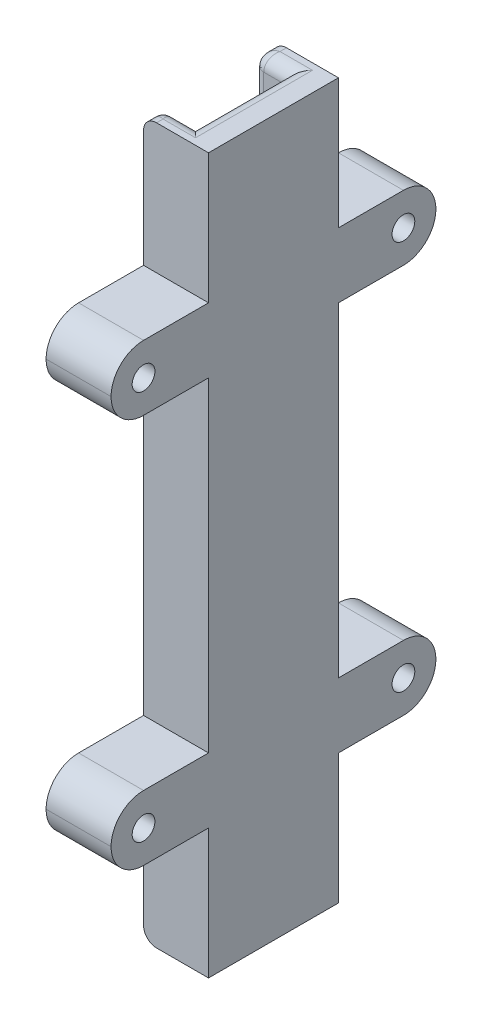
SolidWorks part; units mm, degrees
ref_plane "Front Plane" through (0, 0, 0) normal (0, 0, 1) x (1, 0, 0)
ref_plane "Top Plane" through (0, 0, 0) normal (0, 1, 0) x (1, 0, 0)
ref_plane "Right Plane" through (0, 0, 0) normal (1, 0, 0) x (0, 0, -1)
sketch "Sketch1" plane through (0, 0, 0) normal (0, 0, 1) x (1, 0, 0)
  line L6 (5, 55) -> (-5, 55)
  line L16 (5, 55) -> (5, -55)
  line L17 (5, -55) -> (-5, -55)
  line L18 (-5, 55) -> (-5, -55)
  line L19 (5, 55) -> (-5, -55) construction
  line L20 (5, -55) -> (-5, 55) construction
  point P0 (0, 0)
  dimension "D1" = 10
  dimension "D2" = 110
extrude "Boss-Extrude5" add sketch "Sketch1" along normal blind 10
sketch "Sketch6" plane through (0, 0, 10) normal (0, 0, 1) x (1, 0, 0)
  line L0 (5, -55) -> (5, 55) construction
  line L5 (-5, 55) -> (-5, -55) construction
  line L10 (-5, 35) -> (5, 35)
  line L11 (-5, 35) -> (-5, 25)
  line L12 (-5, 25) -> (5, 25)
  line L13 (5, 35) -> (5, 25)
  line L15 (-5, -25) -> (5, -25)
  line L16 (-5, -25) -> (-5, -35)
  line L17 (-5, -35) -> (5, -35)
  line L18 (5, -25) -> (5, -35)
  dimension "D1" = 10
  dimension "D2" = 25
  dimension "D3" = 25
extrude "Boss-Extrude6" add sketch "Sketch6" along normal blind 15
mirror "Mirror2" about plane through (0, 0, 0) normal (0, 0, 1) of "Boss-Extrude6", "Boss-Extrude5"
sketch "Sketch8" plane through (-5, 0, 0) normal (-1, 0, 0) x (0, 0, 1)
  line L2 (-25, 25) -> (-10, 25) construction
  line L5 (-25, -35) -> (-10, -35) construction
  line L6 (25, 35) -> (25, 25) construction
  line L7 (-25, 35) -> (-25, 25) construction
  circle A4 centre (-20, 30) radius 1.75
  circle A5 centre (20, 30) radius 1.75
  circle A6 centre (-20, -30) radius 1.75
  circle A7 centre (20, -30) radius 1.75
  dimension "D3" = 3.5
  dimension "D1" = 5
  dimension "D2" = 5
  dimension "D6" = 5
  dimension "D7" = 5
extrude "Cut-Extrude1" cut sketch "Sketch8" against normal up to next
sketch "Sketch9" plane through (-5, 0, 0) normal (-1, 0, 0) x (0, 0, 1)
  line L0 (10, -55) -> (-10, -55) construction
  line L1 (7, 55) -> (-7, 55)
  line L2 (7, 55) -> (7, -55)
  line L3 (7, -55) -> (-7, -55)
  line L4 (-7, 55) -> (-7, -55)
  line L5 (7, 55) -> (-7, -55) construction
  line L6 (7, -55) -> (-7, 55) construction
  point P0 (0, 0)
  dimension "D1" = 14
extrude "Cut-Extrude2" cut sketch "Sketch9" against normal blind 5
fillet "Fillet2" radius 1.5 2 edges at (-5, 0, 7) (-5, 0, -7)
fillet "Fillet3" radius 5 8 edges at (0, -35, -25) (0, -25, -25) (0, 25, -25) (0, 35, -25) (0, -35, 25) (0, -25, 25) (0, 25, 25) (0, 35, 25)
fillet "Fillet6" [suppressed] radius 2.5
fillet "Fillet8" [suppressed] radius 0.5
fillet "Fillet9" [suppressed] radius 0.5
fillet "Fillet10" radius 2 14 edges at (-5, -55, 9.25) (-1.75, -55, 7) (-1.75, -55, -7) (-5, -55, -9.25) (-1.75, 55, 7) (-5, 55, 9.25) (-5, 55, -9.25) (-1.75, 55, -7) (-4.5607, -55, 7.4393) (0, -55, 0) (-4.5607, -55, -7.4393) (0, 55, 0) (-4.5607, 55, 7.4393) (-4.5607, 55, -7.4393)
